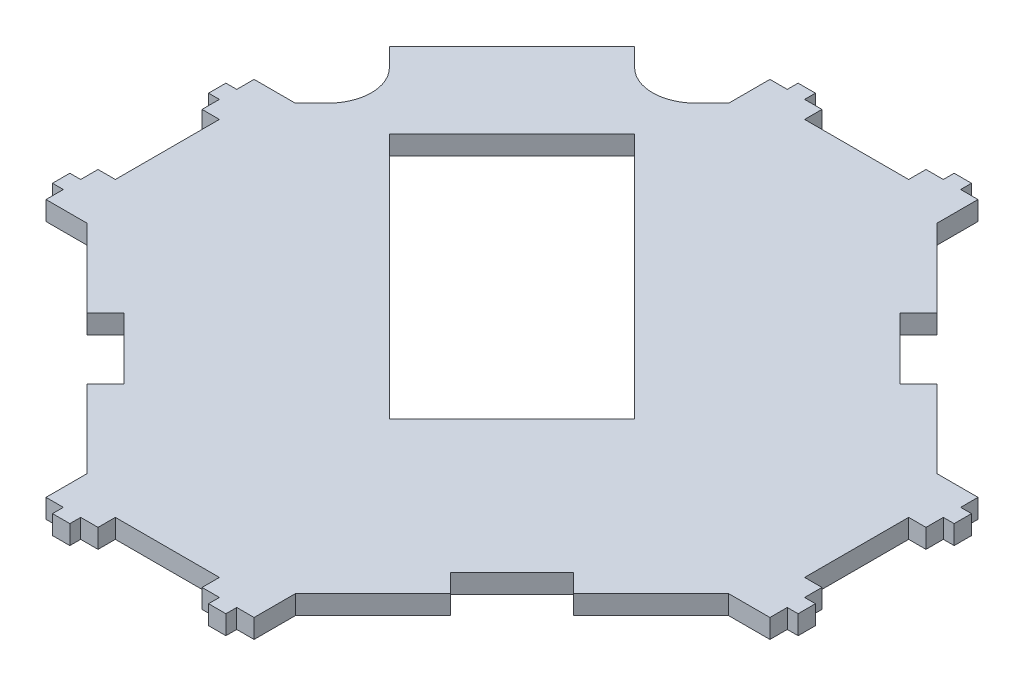
SolidWorks part; units mm, degrees
material "cardboard"
ref_plane "Front Plane" through (0, 0, 0) normal (0, 0, 1) x (1, 0, 0)
ref_plane "Top Plane" through (0, 0, 0) normal (0, 1, 0) x (1, 0, 0)
ref_plane "Right Plane" through (0, 0, 0) normal (1, 0, 0) x (0, 0, -1)
sketch "Sketch1" plane through (0, 0, 0) normal (0, 1, 0) x (1, 0, 0)
  line L0 (73.5822, 10.383) -> (66.732, 6.4281)
  line L1 (99.0822, -13.617) -> (105.9323, -9.662)
  line L2 (114.232, 6.4281) -> (105.9323, 6.4281)
  line L3 (114.232, -9.662) -> (105.9323, -9.662)
  line L4 (66.732, 6.4281) -> (58.4323, 6.4281)
  line L5 (121.0822, 10.383) -> (114.232, 6.4281)
  line L6 (121.0822, -13.617) -> (114.232, -9.662)
  line L7 (99.0822, 10.383) -> (105.9323, 6.4281)
  line L8 (121.0822, 10.383) -> (133.8322, 10.383)
  line L9 (121.0822, -13.617) -> (157.8322, -13.617)
  line L10 (51.5822, 10.383) -> (58.4323, 6.4281)
  line L11 (51.5822, -13.617) -> (58.4323, -9.662)
  line L12 (73.5822, -13.617) -> (66.732, -9.662)
  line L13 (66.732, -9.662) -> (58.4323, -9.662)
  line L14 (73.5822, 10.383) -> (99.0822, 10.383)
  line L15 (73.5822, -13.617) -> (99.0822, -13.617)
  line L16 (-16.1678, 76.133) -> (-12.2129, 69.2829)
  line L17 (7.8322, 101.633) -> (3.8772, 108.4832)
  line L18 (-12.2129, 116.7829) -> (-12.2129, 108.4832)
  line L19 (3.8772, 116.7829) -> (3.8772, 108.4832)
  line L20 (-12.2129, 69.2829) -> (-12.2129, 60.9832)
  line L21 (-16.1678, 123.633) -> (-12.2129, 116.7829)
  line L22 (7.8322, 123.633) -> (3.8772, 116.7829)
  line L23 (-16.1678, 101.633) -> (-12.2129, 108.4832)
  line L24 (-16.1678, 123.633) -> (-16.1678, 136.383)
  line L25 (7.8322, 123.633) -> (7.8322, 160.383)
  line L26 (-16.1678, 54.133) -> (-12.2129, 60.9832)
  line L27 (7.8322, 54.133) -> (3.8772, 60.9832)
  line L28 (7.8322, 76.133) -> (3.8772, 69.2829)
  line L29 (3.8772, 69.2829) -> (3.8772, 60.9832)
  line L30 (-16.1678, 76.133) -> (-16.1678, 101.633)
  line L31 (7.8322, 76.133) -> (7.8322, 101.633)
  line L32 (86.3322, 35.383) -> (86.3322, 15.383)
  line L33 (85.3322, 35.383) -> (85.3322, 29.383)
  line L34 (32.8322, 10.383) -> (38.8322, 10.383)
  line L35 (85.3322, 29.383) -> (87.3322, 29.383)
  line L36 (37.5822, 10.383) -> (37.5822, 8.383)
  line L37 (38.8322, 10.383) -> (51.5822, 10.383)
  line L38 (133.8322, 10.383) -> (133.8322, -13.617)
  line L39 (133.8322, 10.383) -> (157.8322, 10.383)
  line L40 (157.8322, 10.383) -> (157.8322, 8.383)
  line L41 (-32.6642, 12.7373) -> (-4.1678, -15.7591)
  line L42 (-32.6642, 12.7373) -> (-18.5221, 26.8794)
  line L43 (-4.1678, -15.7591) -> (9.9743, -1.617)
  line L44 (-18.5221, 26.8794) -> (9.9743, -1.617)
  line L45 (133.8322, 10.383) -> (133.8322, 35.383)
  line L46 (35.8322, 35.383) -> (157.8322, 35.383)
  line L47 (157.8322, 35.383) -> (157.8322, 10.383)
  line L48 (87.3322, 29.383) -> (87.3322, 21.383)
  line L49 (133.8322, 35.383) -> (133.8322, 59.383)
  line L50 (133.8322, 59.383) -> (142.8322, 59.383)
  line L51 (38.8322, 35.383) -> (38.8322, 15.383)
  line L52 (157.8322, 59.383) -> (157.8322, 49.705)
  line L53 (142.8322, 59.383) -> (142.8322, 61.583)
  line L54 (148.8322, 61.583) -> (148.8322, 59.383)
  line L55 (148.8322, 59.383) -> (157.8322, 59.383)
  line L56 (-63.1678, 136.383) -> (-63.1678, 111.883)
  line L57 (-43.1678, 111.883) -> (-43.1678, 136.383)
  line L58 (87.3322, 21.383) -> (85.3322, 21.383)
  line L59 (133.8322, -13.617) -> (133.8322, -38.617)
  line L60 (142.8322, -38.617) -> (148.8322, -38.617)
  line L61 (157.8322, -38.617) -> (157.8322, -13.617)
  line L62 (38.8322, -38.617) -> (38.8322, -18.617)
  line L63 (133.8322, -38.617) -> (133.8322, -39.797)
  line L64 (148.8322, -39.797) -> (157.8322, -39.797)
  line L65 (157.8322, -39.797) -> (157.8322, -38.617)
  line L66 (142.8322, -39.797) -> (142.8322, -38.617)
  line L67 (148.8322, -39.797) -> (148.8322, -38.617)
  line L68 (-42.3478, -139.617) -> (-42.3478, -148.617)
  line L69 (85.3322, 21.383) -> (85.3322, 15.383)
  line L70 (85.3322, 10.383) -> (85.3322, 2.383)
  line L71 (38.8322, -13.617) -> (51.5822, -13.617)
  line L72 (32.8322, -13.617) -> (38.8322, -13.617)
  line L73 (86.306, 10.383) -> (86.306, -13.617)
  line L74 (85.3322, 2.383) -> (87.3322, 2.383)
  line L75 (87.3322, 2.383) -> (87.3322, -5.617)
  line L76 (87.3322, -5.617) -> (85.3322, -5.617)
  line L77 (131.8322, 10.383) -> (131.8322, 2.383)
  line L78 (131.8322, 2.383) -> (135.8322, 2.383)
  line L79 (34.0122, 160.383) -> (34.0122, 151.383)
  line L80 (33.8322, 33.383) -> (33.8322, 17.383)
  line L81 (35.8322, 15.383) -> (133.8322, 15.383)
  line L82 (37.5822, 22.383) -> (37.5822, 15.383)
  line L83 (38.8322, 28.383) -> (35.8322, 28.383)
  line L84 (35.8322, 28.383) -> (35.8322, 22.383)
  line L85 (40.0822, 4.383) -> (37.5822, 4.383)
  line L86 (1.8322, -43.367) -> (1.8322, -41.367)
  line L87 (37.5822, -7.617) -> (40.0822, -7.617)
  line L88 (40.0822, 4.383) -> (40.0822, -7.617)
  line L89 (38.8322, 10.383) -> (38.8322, 4.383)
  line L90 (37.5822, 8.383) -> (40.0822, 8.383)
  line L91 (40.0822, 8.383) -> (40.0822, 6.383)
  line L92 (40.0822, 6.383) -> (37.5822, 6.383)
  line L93 (37.5822, 6.383) -> (37.5822, 4.383)
  line L94 (37.5822, -9.617) -> (37.5822, -7.617)
  line L95 (40.0822, -9.617) -> (37.5822, -9.617)
  line L96 (40.0822, -11.617) -> (40.0822, -9.617)
  line L97 (37.5822, -11.617) -> (40.0822, -11.617)
  line L98 (37.5822, -13.617) -> (37.5822, -11.617)
  line L99 (135.8322, 2.383) -> (135.8322, -5.617)
  line L100 (135.8322, -5.617) -> (131.8322, -5.617)
  line L101 (131.8322, -5.617) -> (131.8322, -13.617)
  line L102 (133.8322, 12.383) -> (141.8322, 12.383)
  line L103 (141.8322, 12.383) -> (141.8322, 8.383)
  line L104 (141.8322, 8.383) -> (149.8322, 8.383)
  line L105 (149.8322, 8.383) -> (149.8322, 12.383)
  line L106 (149.8322, 12.383) -> (157.8322, 12.383)
  line L107 (132.3322, 35.383) -> (132.3322, 29.383)
  line L108 (132.3322, 29.383) -> (135.3322, 29.383)
  line L109 (135.3322, 29.383) -> (135.3322, 21.383)
  line L110 (135.3322, 21.383) -> (132.3322, 21.383)
  line L111 (132.3322, 21.383) -> (132.3322, 15.383)
  line L112 (85.3322, -5.617) -> (85.3322, -13.617)
  line L113 (85.3322, -24.617) -> (85.3322, -18.617)
  line L114 (86.3322, -38.617) -> (86.3322, -18.617)
  line L115 (87.3322, -24.617) -> (85.3322, -24.617)
  line L116 (87.3322, -32.617) -> (87.3322, -24.617)
  line L117 (149.8322, -15.617) -> (157.8322, -15.617)
  line L118 (149.8322, -11.617) -> (149.8322, -15.617)
  line L119 (141.8322, -11.617) -> (149.8322, -11.617)
  line L120 (141.8322, -15.617) -> (141.8322, -11.617)
  line L121 (133.8322, -15.617) -> (141.8322, -15.617)
  line L122 (132.3322, -24.617) -> (132.3322, -18.617)
  line L123 (135.3322, -24.617) -> (132.3322, -24.617)
  line L124 (37.5822, 35.383) -> (37.5822, 28.383)
  line L125 (38.8322, 22.383) -> (35.8322, 22.383)
  line L126 (133.8322, -38.617) -> (35.8322, -38.617)
  line L127 (33.8322, -36.617) -> (33.8322, -20.617)
  line L128 (35.8322, -18.617) -> (133.8322, -18.617)
  line L129 (135.3322, -32.617) -> (135.3322, -24.617)
  line L130 (132.3322, -32.617) -> (135.3322, -32.617)
  line L131 (132.3322, -38.617) -> (132.3322, -32.617)
  line L132 (85.3322, -32.617) -> (87.3322, -32.617)
  line L133 (85.3322, -38.617) -> (85.3322, -32.617)
  line L134 (133.8322, 37.383) -> (141.8322, 37.383)
  line L135 (141.8322, 37.383) -> (141.8322, 33.383)
  line L136 (141.8322, 33.383) -> (149.8322, 33.383)
  line L137 (149.8322, 33.383) -> (149.8322, 37.383)
  line L138 (149.8322, 37.383) -> (157.8322, 37.383)
  line L139 (-48.6678, 132.133) -> (-48.6678, 116.133)
  line L140 (-60.1678, 132.133) -> (-57.6678, 132.133)
  line L141 (-60.1678, 132.133) -> (-60.1678, 116.133)
  line L142 (-60.1678, 116.133) -> (-57.6678, 116.133)
  line L143 (-57.6678, 132.133) -> (-57.6678, 116.133)
  line L144 (37.5822, -25.617) -> (37.5822, -18.617)
  line L145 (38.8322, -25.617) -> (35.8322, -25.617)
  line L146 (35.8322, -31.617) -> (35.8322, -25.617)
  line L147 (38.8322, -31.617) -> (35.8322, -31.617)
  line L148 (37.5822, -38.617) -> (37.5822, -31.617)
  line L149 (192.8322, 3.383) -> (192.8322, -6.617)
  line L150 (187.8322, 8.383) -> (157.8322, 8.383)
  line L151 (187.8322, -11.617) -> (157.8322, -11.617)
  line L152 (187.8322, 8.383) -> (192.8322, 3.383)
  line L153 (192.8322, -6.617) -> (187.8322, -11.617)
  line L154 (157.8322, -11.617) -> (157.8322, -13.617)
  line L155 (133.8322, 61.583) -> (142.8322, 61.583)
  line L156 (133.8322, 61.583) -> (133.8322, 63.583)
  line L157 (133.8322, 63.583) -> (157.8322, 63.583)
  line L158 (157.8322, 63.583) -> (157.8322, 61.583)
  line L159 (148.8322, 61.583) -> (157.8322, 61.583)
  line L160 (-46.1678, 116.133) -> (-48.6678, 116.133)
  line L161 (-46.1678, 132.133) -> (-46.1678, 116.133)
  line L162 (-46.1678, 132.133) -> (-48.6678, 132.133)
  line L163 (151.2322, 49.705) -> (157.8322, 49.705)
  line L164 (151.2322, 49.705) -> (151.2322, 45.205)
  line L165 (151.2322, 45.205) -> (157.8322, 45.205)
  line L166 (157.8322, 45.205) -> (157.8322, 35.383)
  line L167 (7.8322, -79.367) -> (3.8772, -72.5168)
  line L168 (-16.1678, -104.867) -> (-12.2129, -111.7171)
  line L169 (3.8772, -120.0168) -> (3.8772, -111.7171)
  line L170 (7.8322, -38.617) -> (7.8322, -44.617)
  line L171 (7.8322, -43.367) -> (5.8322, -43.367)
  line L172 (7.8322, -44.617) -> (7.8322, -57.367)
  line L173 (-12.2129, -120.0168) -> (-12.2129, -111.7171)
  line L174 (3.8772, -72.5168) -> (3.8772, -64.2171)
  line L175 (7.8322, -126.867) -> (3.8772, -120.0168)
  line L176 (-16.1678, -126.867) -> (-12.2129, -120.0168)
  line L177 (7.8322, -104.867) -> (3.8772, -111.7171)
  line L178 (7.8322, -126.867) -> (7.8322, -139.617)
  line L179 (-16.1678, -126.867) -> (-16.1678, -163.617)
  line L180 (7.8322, -57.367) -> (3.8772, -64.2171)
  line L181 (-16.1678, -57.367) -> (-12.2129, -64.2171)
  line L182 (32.8322, -44.617) -> (12.8322, -44.617)
  line L183 (-16.1678, -79.367) -> (-12.2129, -72.5168)
  line L184 (-12.2129, -72.5168) -> (-12.2129, -64.2171)
  line L185 (7.8322, -79.367) -> (7.8322, -104.867)
  line L186 (-16.1678, -79.367) -> (-16.1678, -104.867)
  line L187 (32.8322, -92.117) -> (12.8322, -92.117)
  line L188 (32.8322, -91.117) -> (26.8322, -91.117)
  line L189 (26.8322, -91.117) -> (26.8322, -93.117)
  line L190 (7.8322, -139.617) -> (-16.1678, -139.617)
  line L191 (7.8322, -139.617) -> (7.8322, -163.617)
  line L192 (7.8322, -163.617) -> (5.8322, -163.617)
  line L193 (7.8322, -139.617) -> (32.8322, -139.617)
  line L194 (32.8322, -41.617) -> (32.8322, -163.617)
  line L195 (-41.1678, -44.617) -> (-21.1678, -44.617)
  line L196 (32.8322, -163.617) -> (7.8322, -163.617)
  line L197 (26.8322, -93.117) -> (18.8322, -93.117)
  line L198 (32.8322, -139.617) -> (56.8322, -139.617)
  line L199 (56.8322, -139.617) -> (56.8322, -148.617)
  line L200 (56.8322, -163.617) -> (47.1541, -163.617)
  line L201 (56.8322, -148.617) -> (59.0322, -148.617)
  line L202 (59.0322, -154.617) -> (56.8322, -154.617)
  line L203 (56.8322, -154.617) -> (56.8322, -163.617)
  line L204 (-16.1678, -44.617) -> (-16.1678, -57.367)
  line L205 (-16.1678, -38.617) -> (-16.1678, -44.617)
  line L206 (18.8322, -93.117) -> (18.8322, -91.117)
  line L207 (-16.1678, -139.617) -> (-41.1678, -139.617)
  line L208 (-41.1678, -148.617) -> (-41.1678, -154.617)
  line L209 (34.0122, 145.383) -> (34.0122, 136.383)
  line L210 (30.8322, -39.617) -> (14.8322, -39.617)
  line L211 (12.8322, -41.617) -> (12.8322, -139.617)
  line L212 (19.8322, -43.367) -> (12.8322, -43.367)
  line L213 (25.8322, -44.617) -> (25.8322, -41.617)
  line L214 (25.8322, -41.617) -> (19.8322, -41.617)
  line L215 (1.8322, -45.867) -> (1.8322, -43.367)
  line L216 (-41.1678, -163.617) -> (-16.1678, -163.617)
  line L217 (-10.1678, -43.367) -> (-10.1678, -45.867)
  line L218 (1.8322, -45.867) -> (-10.1678, -45.867)
  line L219 (7.8322, -44.617) -> (1.8322, -44.617)
  line L220 (5.8322, -43.367) -> (5.8322, -45.867)
  line L221 (5.8322, -45.867) -> (3.8322, -45.867)
  line L222 (3.8322, -45.867) -> (3.8322, -43.367)
  line L223 (3.8322, -43.367) -> (1.8322, -43.367)
  line L224 (-12.1678, -43.367) -> (-10.1678, -43.367)
  line L225 (-12.1678, -45.867) -> (-12.1678, -43.367)
  line L226 (-14.1678, -45.867) -> (-12.1678, -45.867)
  line L227 (-14.1678, -43.367) -> (-14.1678, -45.867)
  line L228 (-16.1678, -43.367) -> (-14.1678, -43.367)
  line L229 (-41.1678, -139.617) -> (-42.3478, -139.617)
  line L230 (-42.3478, -154.617) -> (-42.3478, -163.617)
  line L231 (-42.3478, -163.617) -> (-41.1678, -163.617)
  line L232 (-42.3478, -148.617) -> (-41.1678, -148.617)
  line L233 (-42.3478, -154.617) -> (-41.1678, -154.617)
  line L234 (-166.1678, 36.563) -> (-157.1678, 36.563)
  line L235 (18.8322, -91.117) -> (12.8322, -91.117)
  line L236 (7.8322, -91.117) -> (-0.1678, -91.117)
  line L237 (7.8322, -92.0907) -> (-16.1678, -92.0907)
  line L238 (-0.1678, -91.117) -> (-0.1678, -93.117)
  line L239 (-0.1678, -93.117) -> (-8.1678, -93.117)
  line L240 (-8.1678, -93.117) -> (-8.1678, -91.117)
  line L241 (7.8322, -137.617) -> (-0.1678, -137.617)
  line L242 (-0.1678, -137.617) -> (-0.1678, -141.617)
  line L243 (-0.1678, -141.617) -> (-8.1678, -141.617)
  line L244 (-8.1678, -141.617) -> (-8.1678, -137.617)
  line L245 (-8.1678, -137.617) -> (-16.1678, -137.617)
  line L246 (9.8322, -139.617) -> (9.8322, -147.617)
  line L247 (9.8322, -147.617) -> (5.8322, -147.617)
  line L248 (5.8322, -147.617) -> (5.8322, -155.617)
  line L249 (5.8322, -155.617) -> (9.8322, -155.617)
  line L250 (9.8322, -155.617) -> (9.8322, -163.617)
  line L251 (32.8322, -138.117) -> (26.8322, -138.117)
  line L252 (26.8322, -138.117) -> (26.8322, -141.117)
  line L253 (26.8322, -141.117) -> (18.8322, -141.117)
  line L254 (32.8322, -43.367) -> (25.8322, -43.367)
  line L255 (19.8322, -44.617) -> (19.8322, -41.617)
  line L256 (-41.1678, -139.617) -> (-41.1678, -41.617)
  line L257 (-39.1678, -39.617) -> (-23.1678, -39.617)
  line L258 (-21.1678, -41.617) -> (-21.1678, -139.617)
  line L259 (18.8322, -141.117) -> (18.8322, -138.117)
  line L260 (18.8322, -138.117) -> (12.8322, -138.117)
  line L261 (-8.1678, -91.117) -> (-16.1678, -91.117)
  line L262 (-27.1678, -91.117) -> (-21.1678, -91.117)
  line L263 (-41.1678, -92.117) -> (-21.1678, -92.117)
  line L264 (-27.1678, -93.117) -> (-27.1678, -91.117)
  line L265 (-35.1678, -93.117) -> (-27.1678, -93.117)
  line L266 (-18.1678, -155.617) -> (-18.1678, -163.617)
  line L267 (-14.1678, -155.617) -> (-18.1678, -155.617)
  line L268 (-14.1678, -147.617) -> (-14.1678, -155.617)
  line L269 (-18.1678, -147.617) -> (-14.1678, -147.617)
  line L270 (-18.1678, -139.617) -> (-18.1678, -147.617)
  line L271 (-27.1678, -138.117) -> (-21.1678, -138.117)
  line L272 (-27.1678, -141.117) -> (-27.1678, -138.117)
  line L273 (-35.1678, -141.117) -> (-27.1678, -141.117)
  line L274 (-28.1678, -43.367) -> (-21.1678, -43.367)
  line L275 (-28.1678, -44.617) -> (-28.1678, -41.617)
  line L276 (-34.1678, -41.617) -> (-28.1678, -41.617)
  line L277 (-34.1678, -44.617) -> (-34.1678, -41.617)
  line L278 (-41.1678, -43.367) -> (-34.1678, -43.367)
  line L279 (-35.1678, -138.117) -> (-35.1678, -141.117)
  line L280 (-41.1678, -138.117) -> (-35.1678, -138.117)
  line L281 (-35.1678, -91.117) -> (-35.1678, -93.117)
  line L282 (-41.1678, -91.117) -> (-35.1678, -91.117)
  line L283 (34.8322, -139.617) -> (34.8322, -147.617)
  line L284 (34.8322, -147.617) -> (30.8322, -147.617)
  line L285 (30.8322, -147.617) -> (30.8322, -155.617)
  line L286 (30.8322, -155.617) -> (34.8322, -155.617)
  line L287 (34.8322, -155.617) -> (34.8322, -163.617)
  line L288 (0.8322, -198.617) -> (-9.1678, -198.617)
  line L289 (5.8322, -193.617) -> (5.8322, -163.617)
  line L290 (-14.1678, -193.617) -> (-14.1678, -163.617)
  line L291 (5.8322, -193.617) -> (0.8322, -198.617)
  line L292 (-9.1678, -198.617) -> (-14.1678, -193.617)
  line L293 (-14.1678, -163.617) -> (-16.1678, -163.617)
  line L294 (59.0322, -139.617) -> (59.0322, -148.617)
  line L295 (59.0322, -139.617) -> (61.0322, -139.617)
  line L296 (61.0322, -139.617) -> (61.0322, -163.617)
  line L297 (61.0322, -163.617) -> (59.0322, -163.617)
  line L298 (59.0322, -154.617) -> (59.0322, -163.617)
  line L299 (-41.1678, -13.617) -> (-47.1678, -13.617)
  line L300 (-45.9178, -13.617) -> (-45.9178, -11.617)
  line L301 (-47.1678, -13.617) -> (-59.9178, -13.617)
  line L302 (47.1541, -157.017) -> (47.1541, -163.617)
  line L303 (47.1541, -157.017) -> (42.6541, -157.017)
  line L304 (-47.1678, -38.617) -> (-47.1678, -18.617)
  line L305 (42.6541, -157.017) -> (42.6541, -163.617)
  line L306 (42.6541, -163.617) -> (32.8322, -163.617)
  line L307 (-81.9178, -13.617) -> (-75.0677, -9.662)
  line L308 (-107.4178, 10.383) -> (-114.268, 6.4281)
  line L309 (-122.5677, -9.662) -> (-114.268, -9.662)
  line L310 (-122.5677, 6.4281) -> (-114.268, 6.4281)
  line L311 (-75.0677, -9.662) -> (-66.768, -9.662)
  line L312 (-129.4178, -13.617) -> (-122.5677, -9.662)
  line L313 (-129.4178, 10.383) -> (-122.5677, 6.4281)
  line L314 (-107.4178, -13.617) -> (-114.268, -9.662)
  line L315 (-129.4178, -13.617) -> (-142.1678, -13.617)
  line L316 (-47.1678, 35.383) -> (-47.1678, 15.383)
  line L317 (-129.4178, 10.383) -> (-166.1678, 10.383)
  line L318 (-59.9178, -13.617) -> (-66.768, -9.662)
  line L319 (-59.9178, 10.383) -> (-66.768, 6.4281)
  line L320 (-81.9178, 10.383) -> (-75.0677, 6.4281)
  line L321 (-75.0677, 6.4281) -> (-66.768, 6.4281)
  line L322 (-81.9178, -13.617) -> (-107.4178, -13.617)
  line L323 (-81.9178, 10.383) -> (-107.4178, 10.383)
  line L324 (-94.6678, -38.617) -> (-94.6678, -18.617)
  line L325 (-47.1678, 10.383) -> (-59.9178, 10.383)
  line L326 (-41.1678, 10.383) -> (-47.1678, 10.383)
  line L327 (-93.6678, -38.617) -> (-93.6678, -32.617)
  line L328 (-93.6678, -32.617) -> (-95.6678, -32.617)
  line L329 (-142.1678, -13.617) -> (-142.1678, 10.383)
  line L330 (-142.1678, -13.617) -> (-166.1678, -13.617)
  line L331 (-166.1678, -13.617) -> (-166.1678, -11.617)
  line L332 (-142.1678, -13.617) -> (-142.1678, -38.617)
  line L333 (133.8322, -39.797) -> (142.8322, -39.797)
  line L334 (-42.1678, -36.617) -> (-42.1678, -20.617)
  line L335 (-44.1678, -18.617) -> (-142.1678, -18.617)
  line L336 (-45.9178, -25.617) -> (-45.9178, -18.617)
  line L337 (-47.1678, -31.617) -> (-44.1678, -31.617)
  line L338 (-44.1678, -31.617) -> (-44.1678, -25.617)
  line L339 (-48.4178, -7.617) -> (-45.9178, -7.617)
  line L340 (-44.1678, -38.617) -> (-166.1678, -38.617)
  line L341 (-45.9178, 4.383) -> (-48.4178, 4.383)
  line L342 (-48.4178, -7.617) -> (-48.4178, 4.383)
  line L343 (-47.1678, -13.617) -> (-47.1678, -7.617)
  line L344 (-45.9178, -11.617) -> (-48.4178, -11.617)
  line L345 (-48.4178, -11.617) -> (-48.4178, -9.617)
  line L346 (-48.4178, -9.617) -> (-45.9178, -9.617)
  line L347 (-45.9178, -9.617) -> (-45.9178, -7.617)
  line L348 (-45.9178, 6.383) -> (-45.9178, 4.383)
  line L349 (-48.4178, 6.383) -> (-45.9178, 6.383)
  line L350 (-48.4178, 8.383) -> (-48.4178, 6.383)
  line L351 (-45.9178, 8.383) -> (-48.4178, 8.383)
  line L352 (-45.9178, 10.383) -> (-45.9178, 8.383)
  line L353 (-166.1678, -38.617) -> (-166.1678, -13.617)
  line L354 (-95.6678, -32.617) -> (-95.6678, -24.617)
  line L355 (-142.1678, -38.617) -> (-142.1678, -62.617)
  line L356 (-142.1678, -62.617) -> (-151.1678, -62.617)
  line L357 (-166.1678, -62.617) -> (-166.1678, -52.9389)
  line L358 (-151.1678, -62.617) -> (-151.1678, -64.817)
  line L359 (-157.1678, -64.817) -> (-157.1678, -62.617)
  line L360 (-157.1678, -62.617) -> (-166.1678, -62.617)
  line L361 (-95.6678, -24.617) -> (-93.6678, -24.617)
  line L362 (-142.1678, 10.383) -> (-142.1678, 35.383)
  line L363 (-151.1678, 35.383) -> (-157.1678, 35.383)
  line L364 (-166.1678, 35.383) -> (-166.1678, 10.383)
  line L365 (-142.1678, 35.383) -> (-142.1678, 36.563)
  line L366 (-166.1678, 36.563) -> (-166.1678, 35.383)
  line L367 (-151.1678, 36.563) -> (-151.1678, 35.383)
  line L368 (-157.1678, 36.563) -> (-157.1678, 35.383)
  line L369 (-151.1678, 36.563) -> (-142.1678, 36.563)
  line L370 (-93.6678, -24.617) -> (-93.6678, -18.617)
  line L371 (-93.6678, -13.617) -> (-93.6678, -5.617)
  line L372 (-94.6416, -13.617) -> (-94.6416, 10.383)
  line L373 (-93.6678, -5.617) -> (-95.6678, -5.617)
  line L374 (-45.9178, -38.617) -> (-45.9178, -31.617)
  line L375 (-47.1678, -25.617) -> (-44.1678, -25.617)
  line L376 (-142.1678, 35.383) -> (-44.1678, 35.383)
  line L377 (-42.1678, 33.383) -> (-42.1678, 17.383)
  line L378 (-44.1678, 15.383) -> (-142.1678, 15.383)
  line L379 (-95.6678, -5.617) -> (-95.6678, 2.383)
  line L380 (-95.6678, 2.383) -> (-93.6678, 2.383)
  line L381 (-140.1678, -13.617) -> (-140.1678, -5.617)
  line L382 (-140.1678, -5.617) -> (-144.1678, -5.617)
  line L383 (-144.1678, -5.617) -> (-144.1678, 2.383)
  line L384 (-144.1678, 2.383) -> (-140.1678, 2.383)
  line L385 (-140.1678, 2.383) -> (-140.1678, 10.383)
  line L386 (-142.1678, -15.617) -> (-150.1678, -15.617)
  line L387 (-150.1678, -15.617) -> (-150.1678, -11.617)
  line L388 (-150.1678, -11.617) -> (-158.1678, -11.617)
  line L389 (-158.1678, -11.617) -> (-158.1678, -15.617)
  line L390 (-158.1678, -15.617) -> (-166.1678, -15.617)
  line L391 (-140.6678, -38.617) -> (-140.6678, -32.617)
  line L392 (-41.1678, 88.883) -> (-21.1678, 88.883)
  line L393 (-41.1678, 87.883) -> (-35.1678, 87.883)
  line L394 (-45.9178, 22.383) -> (-45.9178, 15.383)
  line L395 (-47.1678, 22.383) -> (-44.1678, 22.383)
  line L396 (-44.1678, 28.383) -> (-44.1678, 22.383)
  line L397 (-47.1678, 28.383) -> (-44.1678, 28.383)
  line L398 (-45.9178, 35.383) -> (-45.9178, 28.383)
  line L399 (-140.6678, -32.617) -> (-143.6678, -32.617)
  line L400 (-143.6678, -32.617) -> (-143.6678, -24.617)
  line L401 (-143.6678, -24.617) -> (-140.6678, -24.617)
  line L402 (-140.6678, -24.617) -> (-140.6678, -18.617)
  line L403 (-93.6678, 2.383) -> (-93.6678, 10.383)
  line L404 (-93.6678, 21.383) -> (-93.6678, 15.383)
  line L405 (-94.6678, 35.383) -> (-94.6678, 15.383)
  line L406 (-95.6678, 21.383) -> (-93.6678, 21.383)
  line L407 (-95.6678, 29.383) -> (-95.6678, 21.383)
  line L408 (-158.1678, 12.383) -> (-166.1678, 12.383)
  line L409 (-158.1678, 8.383) -> (-158.1678, 12.383)
  line L410 (-150.1678, 8.383) -> (-158.1678, 8.383)
  line L411 (-150.1678, 12.383) -> (-150.1678, 8.383)
  line L412 (-142.1678, 12.383) -> (-150.1678, 12.383)
  line L413 (-140.6678, 21.383) -> (-140.6678, 15.383)
  line L414 (-143.6678, 21.383) -> (-140.6678, 21.383)
  line L415 (-143.6678, 29.383) -> (-143.6678, 21.383)
  line L416 (-140.6678, 29.383) -> (-143.6678, 29.383)
  line L417 (-140.6678, 35.383) -> (-140.6678, 29.383)
  line L418 (-93.6678, 29.383) -> (-95.6678, 29.383)
  line L419 (-93.6678, 35.383) -> (-93.6678, 29.383)
  line L420 (-142.1678, -40.617) -> (-150.1678, -40.617)
  line L421 (-150.1678, -40.617) -> (-150.1678, -36.617)
  line L422 (-150.1678, -36.617) -> (-158.1678, -36.617)
  line L423 (-158.1678, -36.617) -> (-158.1678, -40.617)
  line L424 (-158.1678, -40.617) -> (-166.1678, -40.617)
  line L425 (-16.1678, 40.133) -> (-14.1678, 40.133)
  line L426 (-35.1678, 87.883) -> (-35.1678, 89.883)
  line L427 (-16.1678, 136.383) -> (7.8322, 136.383)
  line L428 (-16.1678, 136.383) -> (-16.1678, 160.383)
  line L429 (-16.1678, 160.383) -> (-14.1678, 160.383)
  line L430 (-16.1678, 136.383) -> (-41.1678, 136.383)
  line L431 (-41.1678, 136.383) -> (-41.1678, 160.383)
  line L432 (-41.1678, 160.383) -> (-16.1678, 160.383)
  line L433 (-41.1678, 136.383) -> (-41.1678, 41.383)
  line L434 (-41.1678, 41.383) -> (-21.1678, 41.383)
  line L435 (-21.1678, 41.383) -> (-21.1678, 136.383)
  line L436 (-35.1678, 89.883) -> (-27.1678, 89.883)
  line L437 (-41.1678, 136.383) -> (-65.1678, 136.383)
  line L438 (-65.1678, 136.383) -> (-65.1678, 145.383)
  line L439 (-65.1678, 160.383) -> (-55.4898, 160.383)
  line L440 (-65.1678, 145.383) -> (-67.3678, 145.383)
  line L441 (-67.3678, 151.383) -> (-65.1678, 151.383)
  line L442 (-65.1678, 151.383) -> (-65.1678, 160.383)
  line L443 (-63.1678, 111.883) -> (-43.1678, 111.883)
  line L444 (32.8322, 41.383) -> (12.8322, 41.383)
  line L445 (-27.1678, 89.883) -> (-27.1678, 87.883)
  line L446 (32.8322, 136.383) -> (32.8322, 41.383)
  line L447 (12.8322, 41.383) -> (12.8322, 136.383)
  line L448 (7.8322, 136.383) -> (32.8322, 136.383)
  line L449 (32.8322, 145.383) -> (32.8322, 151.383)
  line L450 (32.8322, 160.383) -> (7.8322, 160.383)
  line L451 (7.8322, 35.383) -> (7.8322, 54.133)
  line L452 (32.8322, 136.383) -> (34.0122, 136.383)
  line L453 (34.0122, 160.383) -> (32.8322, 160.383)
  line L454 (34.0122, 145.383) -> (32.8322, 145.383)
  line L455 (34.0122, 151.383) -> (32.8322, 151.383)
  line L456 (-41.1678, 41.383) -> (-41.1678, 38.383)
  line L457 (-39.1678, 36.383) -> (-23.1678, 36.383)
  line L458 (-21.1678, 38.383) -> (-21.1678, 41.383)
  line L459 (30.8322, 36.383) -> (14.8322, 36.383)
  line L460 (12.8322, 38.383) -> (12.8322, 41.383)
  line L461 (-10.1678, 42.633) -> (-10.1678, 40.133)
  line L462 (-27.1678, 87.883) -> (-21.1678, 87.883)
  line L463 (1.8322, 40.133) -> (1.8322, 42.633)
  line L464 (-10.1678, 42.633) -> (1.8322, 42.633)
  line L465 (-16.1678, 41.383) -> (-10.1678, 41.383)
  line L466 (-14.1678, 40.133) -> (-14.1678, 42.633)
  line L467 (-14.1678, 42.633) -> (-12.1678, 42.633)
  line L468 (-12.1678, 42.633) -> (-12.1678, 40.133)
  line L469 (-12.1678, 40.133) -> (-10.1678, 40.133)
  line L470 (3.8322, 40.133) -> (1.8322, 40.133)
  line L471 (3.8322, 42.633) -> (3.8322, 40.133)
  line L472 (5.8322, 42.633) -> (3.8322, 42.633)
  line L473 (5.8322, 40.133) -> (5.8322, 42.633)
  line L474 (7.8322, 40.133) -> (5.8322, 40.133)
  line L475 (-16.1678, 87.883) -> (-8.1678, 87.883)
  line L476 (-16.1678, 88.8568) -> (7.8322, 88.8568)
  line L477 (-8.1678, 87.883) -> (-8.1678, 89.883)
  line L478 (-8.1678, 89.883) -> (-0.1678, 89.883)
  line L479 (-0.1678, 89.883) -> (-0.1678, 87.883)
  line L480 (-16.1678, 134.383) -> (-8.1678, 134.383)
  line L481 (-8.1678, 134.383) -> (-8.1678, 138.383)
  line L482 (-8.1678, 138.383) -> (-0.1678, 138.383)
  line L483 (-0.1678, 138.383) -> (-0.1678, 134.383)
  line L484 (-0.1678, 134.383) -> (7.8322, 134.383)
  line L485 (-18.1678, 136.383) -> (-18.1678, 144.383)
  line L486 (-18.1678, 144.383) -> (-14.1678, 144.383)
  line L487 (-14.1678, 144.383) -> (-14.1678, 152.383)
  line L488 (-14.1678, 152.383) -> (-18.1678, 152.383)
  line L489 (-18.1678, 152.383) -> (-18.1678, 160.383)
  line L490 (-41.1678, 134.883) -> (-35.1678, 134.883)
  line L491 (-35.1678, 134.883) -> (-35.1678, 137.883)
  line L492 (-35.1678, 137.883) -> (-27.1678, 137.883)
  line L493 (-27.1678, 137.883) -> (-27.1678, 134.883)
  line L494 (-27.1678, 134.883) -> (-21.1678, 134.883)
  line L495 (-0.1678, 87.883) -> (7.8322, 87.883)
  line L496 (18.8322, 87.883) -> (12.8322, 87.883)
  line L497 (32.8322, 88.883) -> (12.8322, 88.883)
  line L498 (18.8322, 89.883) -> (18.8322, 87.883)
  line L499 (26.8322, 89.883) -> (18.8322, 89.883)
  line L500 (-41.1678, 40.133) -> (-34.1678, 40.133)
  line L501 (25.8322, 38.383) -> (19.8322, 38.383)
  line L502 (19.8322, 40.133) -> (12.8322, 40.133)
  line L503 (-34.1678, 41.383) -> (-34.1678, 38.383)
  line L504 (-28.1678, 40.133) -> (-21.1678, 40.133)
  line L505 (9.8322, 152.383) -> (9.8322, 160.383)
  line L506 (5.8322, 152.383) -> (9.8322, 152.383)
  line L507 (5.8322, 144.383) -> (5.8322, 152.383)
  line L508 (9.8322, 144.383) -> (5.8322, 144.383)
  line L509 (9.8322, 136.383) -> (9.8322, 144.383)
  line L510 (18.8322, 134.883) -> (12.8322, 134.883)
  line L511 (18.8322, 137.883) -> (18.8322, 134.883)
  line L512 (26.8322, 137.883) -> (18.8322, 137.883)
  line L513 (26.8322, 134.883) -> (26.8322, 137.883)
  line L514 (32.8322, 134.883) -> (26.8322, 134.883)
  line L515 (26.8322, 87.883) -> (26.8322, 89.883)
  line L516 (32.8322, 87.883) -> (26.8322, 87.883)
  line L517 (7.8322, 35.383) -> (16.7966, 26.4186)
  line L518 (32.8322, -13.617) -> (23.8677, -22.5814)
  line L519 (-16.1678, -38.617) -> (-25.1323, -29.6525)
  line L520 (19.8322, 41.383) -> (19.8322, 38.383)
  line L521 (-28.1678, 41.383) -> (-28.1678, 38.383)
  line L522 (25.8322, 41.383) -> (25.8322, 38.383)
  line L523 (32.8322, 40.133) -> (25.8322, 40.133)
  line L524 (-43.1678, 136.383) -> (-43.1678, 144.383)
  line L525 (-43.1678, 144.383) -> (-39.1678, 144.383)
  line L526 (-39.1678, 144.383) -> (-39.1678, 152.383)
  line L527 (-39.1678, 152.383) -> (-43.1678, 152.383)
  line L528 (-43.1678, 152.383) -> (-43.1678, 160.383)
  line L529 (-63.1678, 134.883) -> (-56.1678, 134.883)
  line L530 (-56.1678, 134.883) -> (-56.1678, 137.883)
  line L531 (-56.1678, 137.883) -> (-50.1678, 137.883)
  line L532 (-50.1678, 137.883) -> (-50.1678, 134.883)
  line L533 (-50.1678, 134.883) -> (-43.1678, 134.883)
  line L534 (-16.1678, 35.383) -> (-16.1678, 54.133)
  line L535 (38.8322, -7.617) -> (38.8322, -13.617)
  line L536 (1.8322, 41.383) -> (7.8322, 41.383)
  line L537 (-47.1678, 4.383) -> (-47.1678, 10.383)
  line L538 (-10.1678, -44.617) -> (-16.1678, -44.617)
  line L539 (-9.1678, 195.383) -> (0.8322, 195.383)
  line L540 (-14.1678, 190.383) -> (-14.1678, 160.383)
  line L541 (5.8322, 190.383) -> (5.8322, 160.383)
  line L542 (-14.1678, 190.383) -> (-9.1678, 195.383)
  line L543 (0.8322, 195.383) -> (5.8322, 190.383)
  line L544 (129.5822, 54.383) -> (113.5822, 54.383)
  line L545 (129.5822, 54.383) -> (129.5822, 51.883)
  line L546 (-201.1678, -6.617) -> (-201.1678, 3.383)
  line L547 (-196.1678, -11.617) -> (-166.1678, -11.617)
  line L548 (-196.1678, 8.383) -> (-166.1678, 8.383)
  line L549 (-196.1678, -11.617) -> (-201.1678, -6.617)
  line L550 (-201.1678, 3.383) -> (-196.1678, 8.383)
  line L551 (-166.1678, 8.383) -> (-166.1678, 10.383)
  line L552 (-142.1678, -64.817) -> (-151.1678, -64.817)
  line L553 (-142.1678, -64.817) -> (-142.1678, -66.817)
  line L554 (-142.1678, -66.817) -> (-166.1678, -66.817)
  line L555 (-166.1678, -66.817) -> (-166.1678, -64.817)
  line L556 (5.8322, 160.383) -> (7.8322, 160.383)
  line L557 (-157.1678, -64.817) -> (-166.1678, -64.817)
  line L558 (129.5822, 51.883) -> (113.5822, 51.883)
  line L559 (113.5822, 54.383) -> (113.5822, 51.883)
  line L560 (129.5822, 42.883) -> (113.5822, 42.883)
  line L561 (129.5822, 40.383) -> (129.5822, 42.883)
  line L562 (129.5822, 40.383) -> (113.5822, 40.383)
  line L563 (113.5822, 40.383) -> (113.5822, 42.883)
  line L564 (132.3322, 57.383) -> (132.3322, 50.383)
  line L565 (132.3322, 50.383) -> (135.3322, 50.383)
  line L566 (-159.5678, -52.9389) -> (-166.1678, -52.9389)
  line L567 (-159.5678, -52.9389) -> (-159.5678, -48.4389)
  line L568 (-159.5678, -48.4389) -> (-166.1678, -48.4389)
  line L569 (-67.3678, 136.383) -> (-67.3678, 145.383)
  line L570 (-67.3678, 136.383) -> (-69.3678, 136.383)
  line L571 (-69.3678, 136.383) -> (-69.3678, 160.383)
  line L572 (-69.3678, 160.383) -> (-67.3678, 160.383)
  line L573 (-67.3678, 151.383) -> (-67.3678, 160.383)
  line L574 (-166.1678, -48.4389) -> (-166.1678, -38.617)
  line L575 (135.3322, 50.383) -> (135.3322, 44.383)
  line L576 (-50.5299, 122.2278) -> (-51.6678, 122.2278)
  line L577 (-55.8058, 126.2691) -> (-54.6678, 126.2691)
  line L578 (-55.8058, 126.2691) -> (-55.8058, 122.2278)
  line L579 (-55.8058, 122.2278) -> (-54.6678, 122.2278)
  line L580 (-54.6678, 126.2691) -> (-54.6678, 122.2278)
  line L581 (-51.6678, 126.2691) -> (-51.6678, 122.2278)
  line L582 (-50.5299, 126.2691) -> (-51.6678, 126.2691)
  line L583 (-50.5299, 126.2691) -> (-50.5299, 122.2278)
  line L584 (135.3322, 44.383) -> (132.3322, 44.383)
  line L585 (132.3322, 44.383) -> (132.3322, 37.383)
  line L586 (109.3322, 37.383) -> (133.8322, 37.383)
  line L587 (109.3322, 57.383) -> (109.3322, 37.383)
  line L588 (133.8322, 57.383) -> (109.3322, 57.383)
  line L589 (51.8322, -135.367) -> (51.8322, -119.367)
  line L590 (51.8322, -135.367) -> (49.3322, -135.367)
  line L591 (-55.4898, 153.783) -> (-55.4898, 160.383)
  line L592 (-55.4898, 153.783) -> (-50.9898, 153.783)
  line L593 (-50.9898, 153.783) -> (-50.9898, 160.383)
  line L594 (-50.9898, 160.383) -> (-41.1678, 160.383)
  line L595 (49.3322, -135.367) -> (49.3322, -119.367)
  line L596 (51.8322, -119.367) -> (49.3322, -119.367)
  line L597 (-18.0612, 33.4896) -> (-16.1678, 35.383)
  line L598 (-25.1323, 33.4896) -> (-27.2536, 35.611)
  line L599 (-39.2744, 19.3475) -> (-41.3957, 21.4688)
  line L600 (-41.3957, 21.4688) -> (-27.2536, 35.611)
  line L601 (1.8322, -41.367) -> (-10.1678, -41.367)
  line L602 (37.5822, 4.383) -> (35.5822, 4.383)
  line L603 (-10.1678, -43.367) -> (-10.1678, -41.367)
  line L604 (37.5822, -7.617) -> (35.5822, -7.617)
  line L605 (35.5822, 4.383) -> (35.5822, -7.617)
  line L606 (-45.9178, -7.617) -> (-43.9178, -7.617)
  line L607 (-43.9178, -7.617) -> (-43.9178, 4.383)
  line L608 (-45.9178, 4.383) -> (-43.9178, 4.383)
  line L609 (-10.1678, 40.133) -> (-10.1678, 38.133)
  line L610 (-10.1678, 38.133) -> (1.8322, 38.133)
  line L611 (1.8322, 40.133) -> (1.8322, 38.133)
  line L612 (-41.1678, 10.383) -> (-39.2744, 12.2764)
  line L613 (-34.1678, 38.383) -> (-28.1678, 38.383)
  line L614 (21.7464, -20.4601) -> (14.6753, -27.5312)
  line L615 (14.6753, 24.2973) -> (21.7464, 17.2262)
  line L616 (21.7464, 17.2262) -> (23.8677, 19.3475)
  line L617 (40.3322, -135.367) -> (40.3322, -119.367)
  line L618 (37.8322, -135.367) -> (40.3322, -135.367)
  line L619 (37.8322, -135.367) -> (37.8322, -119.367)
  line L620 (37.8322, -119.367) -> (40.3322, -119.367)
  line L621 (54.8322, -138.117) -> (47.8322, -138.117)
  line L622 (47.8322, -138.117) -> (47.8322, -141.117)
  line L623 (47.8322, -141.117) -> (41.8322, -141.117)
  line L624 (41.8322, -141.117) -> (41.8322, -138.117)
  line L625 (41.8322, -138.117) -> (34.8322, -138.117)
  line L626 (34.8322, -115.117) -> (34.8322, -139.617)
  line L627 (54.8322, -115.117) -> (34.8322, -115.117)
  line L628 (54.8322, -139.617) -> (54.8322, -115.117)
  line L629 (-137.9178, -57.617) -> (-121.9178, -57.617)
  line L630 (-137.9178, -57.617) -> (-137.9178, -55.117)
  line L631 (-137.9178, -55.117) -> (-121.9178, -55.117)
  line L632 (-121.9178, -57.617) -> (-121.9178, -55.117)
  line L633 (-137.9178, -46.117) -> (-121.9178, -46.117)
  line L634 (-137.9178, -43.617) -> (-137.9178, -46.117)
  line L635 (-137.9178, -43.617) -> (-121.9178, -43.617)
  line L636 (-121.9178, -43.617) -> (-121.9178, -46.117)
  line L637 (-140.6678, -60.617) -> (-140.6678, -53.617)
  line L638 (-140.6678, -53.617) -> (-143.6678, -53.617)
  line L639 (-143.6678, -53.617) -> (-143.6678, -47.617)
  line L640 (-143.6678, -47.617) -> (-140.6678, -47.617)
  line L641 (-140.6678, -47.617) -> (-140.6678, -40.617)
  line L642 (-117.6678, -40.617) -> (-142.1678, -40.617)
  line L643 (-117.6678, -60.617) -> (-117.6678, -40.617)
  line L644 (-142.1678, -60.617) -> (-117.6678, -60.617)
  line L645 (123.7183, 50.021) -> (119.677, 50.021)
  line L646 (123.7183, 50.021) -> (123.7183, 48.883)
  line L647 (123.7183, 48.883) -> (119.677, 48.883)
  line L648 (119.677, 50.021) -> (119.677, 48.883)
  line L649 (123.7183, 45.883) -> (119.677, 45.883)
  line L650 (14.6753, 24.2973) -> (16.7966, 26.4186)
  line L651 (123.7183, 44.7451) -> (123.7183, 45.883)
  line L652 (123.7183, 44.7451) -> (119.677, 44.7451)
  line L653 (119.677, 44.7451) -> (119.677, 45.883)
  line L654 (47.4701, -129.503) -> (47.4701, -125.4618)
  line L655 (47.4701, -129.503) -> (46.3322, -129.503)
  line L656 (46.3322, -129.503) -> (46.3322, -125.4618)
  line L657 (47.4701, -125.4618) -> (46.3322, -125.4618)
  line L658 (43.3322, -129.503) -> (43.3322, -125.4618)
  line L659 (42.1942, -129.503) -> (43.3322, -129.503)
  line L660 (42.1942, -129.503) -> (42.1942, -125.4618)
  line L661 (42.1942, -125.4618) -> (43.3322, -125.4618)
  line L662 (-132.0539, -53.2549) -> (-128.0126, -53.2549)
  line L663 (-132.0539, -53.2549) -> (-132.0539, -52.117)
  line L664 (-132.0539, -52.117) -> (-128.0126, -52.117)
  line L665 (-128.0126, -53.2549) -> (-128.0126, -52.117)
  line L666 (-132.0539, -49.117) -> (-128.0126, -49.117)
  line L667 (-132.0539, -47.979) -> (-132.0539, -49.117)
  line L668 (-132.0539, -47.979) -> (-128.0126, -47.979)
  line L669 (-128.0126, -47.979) -> (-128.0126, -49.117)
  line L670 (23.8677, 19.3475) -> (32.8322, 10.383)
  line L671 (14.6753, -27.5312) -> (16.7966, -29.6525)
  line L672 (21.7464, -20.4601) -> (23.8677, -22.5814)
  line L673 (-23.011, -27.5312) -> (-30.082, -20.4601)
  line L674 (-30.082, -20.4601) -> (-32.2034, -22.5814)
  line L675 (-23.011, -27.5312) -> (-25.1323, -29.6525)
  line L676 (16.7966, -29.6525) -> (7.8322, -38.617)
  line L677 (-32.2034, -22.5814) -> (-41.1678, -13.617)
  line L678 (32.8322, 41.383) -> (32.8322, 38.383)
  circle A0 centre (152.5497, 40.6655) radius 1.5
  circle A1 centre (139.1147, 54.1006) radius 1.5
  circle A2 centre (151.489, 53.0399) radius 1.5
  circle A3 centre (140.1753, 41.7262) radius 1.5
  circle A4 centre (145.8322, 47.383) radius 3.1
  circle A5 centre (145.8322, 22.883) radius 5
  circle A6 centre (145.8322, -26.117) radius 5
  circle A7 centre (62.5822, 25.383) radius 5
  circle A8 centre (109.8328, 25.383) radius 5
  circle A9 centre (62.5822, -28.617) radius 5
  circle A10 centre (109.8328, -28.617) radius 5
  circle A11 centre (145.8322, -1.617) radius 7
  circle A12 centre (38.1147, -158.3345) radius 1.5
  circle A13 centre (51.5497, -144.8994) radius 1.5
  circle A14 centre (50.489, -157.2738) radius 1.5
  circle A15 centre (39.1753, -145.9601) radius 1.5
  circle A16 centre (44.8322, -151.617) radius 3.1
  circle A17 centre (20.3322, -151.617) radius 5
  circle A18 centre (-46.4503, 155.1006) radius 1.5
  circle A19 centre (-59.8853, 141.6655) radius 1.5
  circle A20 centre (-58.8247, 154.0399) radius 1.5
  circle A21 centre (-47.511, 142.7262) radius 1.5
  circle A22 centre (-53.1678, 148.383) radius 3.1
  circle A23 centre (-28.6678, -151.617) radius 5
  circle A24 centre (22.8322, -68.367) radius 5
  circle A25 centre (22.8322, -115.6175) radius 5
  circle A26 centre (-31.1678, -68.367) radius 5
  circle A27 centre (-31.1678, -115.6175) radius 5
  circle A28 centre (-4.1678, -151.617) radius 7
  circle A29 centre (-160.8853, -43.8994) radius 1.5
  circle A30 centre (-28.6678, 148.383) radius 5
  circle A31 centre (20.3322, 148.383) radius 5
  circle A32 centre (-147.4503, -57.3345) radius 1.5
  circle A33 centre (-159.8247, -56.2738) radius 1.5
  circle A34 centre (-148.511, -44.9601) radius 1.5
  circle A35 centre (-154.1678, -50.617) radius 3.1
  circle A36 centre (-154.1678, -26.117) radius 5
  circle A37 centre (-154.1678, 22.883) radius 5
  circle A38 centre (-70.9178, -28.617) radius 5
  circle A39 centre (-118.1684, -28.617) radius 5
  circle A40 centre (-70.9178, 25.383) radius 5
  circle A41 centre (-118.1684, 25.383) radius 5
  circle A42 centre (-154.1678, -1.617) radius 7
  circle A43 centre (-31.1678, 65.133) radius 5
  circle A44 centre (-31.1678, 112.3836) radius 5
  circle A45 centre (22.8322, 65.133) radius 5
  circle A46 centre (22.8322, 112.3836) radius 5
  arc A47 (35.8322, 35.383) -> (33.8322, 33.383) centre (35.8322, 33.383) ccw
  arc A48 (33.8322, 17.383) -> (35.8322, 15.383) centre (35.8322, 17.383) ccw
  arc A49 (-23.1678, 36.383) -> (-21.1678, 38.383) centre (-23.1678, 38.383) ccw
  arc A50 (-41.1678, 38.383) -> (-39.1678, 36.383) centre (-39.1678, 38.383) ccw
  arc A51 (32.8322, 38.383) -> (30.8322, 36.383) centre (30.8322, 38.383) cw
  arc A52 (14.8322, 36.383) -> (12.8322, 38.383) centre (14.8322, 38.383) cw
  arc A53 (35.8322, -38.617) -> (33.8322, -36.617) centre (35.8322, -36.617) cw
  arc A54 (33.8322, -20.617) -> (35.8322, -18.617) centre (35.8322, -20.617) cw
  arc A55 (32.8322, -41.617) -> (30.8322, -39.617) centre (30.8322, -41.617) ccw
  arc A56 (14.8322, -39.617) -> (12.8322, -41.617) centre (14.8322, -41.617) ccw
  arc A57 (-41.1678, -41.617) -> (-39.1678, -39.617) centre (-39.1678, -41.617) cw
  arc A58 (-23.1678, -39.617) -> (-21.1678, -41.617) centre (-23.1678, -41.617) cw
  arc A59 (-44.1678, -38.617) -> (-42.1678, -36.617) centre (-44.1678, -36.617) ccw
  arc A60 (-42.1678, -20.617) -> (-44.1678, -18.617) centre (-44.1678, -20.617) ccw
  arc A61 (-44.1678, 35.383) -> (-42.1678, 33.383) centre (-44.1678, 33.383) cw
  arc A62 (-42.1678, 17.383) -> (-44.1678, 15.383) centre (-44.1678, 17.383) cw
  arc A63 (-18.0612, 33.4896) -> (-25.1323, 33.4896) centre (-21.5968, 37.0252) cw
  arc A64 (-39.2744, 19.3475) -> (-39.2744, 12.2764) centre (-42.81, 15.812) cw
  circle A65 centre (-4.1678, 148.383) radius 7
  point P195 (-4.1678, -1.617)
  point P591 (-4.1678, -1.617)
  point P597 (-4.1678, -1.617)
  point P598 (-4.1678, -1.617)
  point P603 (-4.1678, -1.617)
  point P606 (-4.1678, -1.617)
  point P632 (-4.1678, -1.617)
  point P663 (-4.1678, -1.617)
  point P689 (-4.1678, -1.617)
  point P718 (-4.1678, -1.617)
  point P719 (-4.1678, -1.617)
  point P743 (-4.1678, -1.617)
  point P747 (-4.1678, -1.617)
  point P787 (-4.1678, -1.617)
  point P813 (-4.1678, -1.617)
  point P820 (-4.1678, -1.617)
  point P833 (-4.1678, -1.617)
  point P865 (-4.1678, -1.617)
  point P890 (-4.1678, -1.617)
  point P895 (-4.1678, -1.617)
  point P915 (-4.1678, -1.617)
extrude "Boss-Extrude1" add sketch "Sketch1" along normal blind 2.2 contours L599 A64 L612 L326 L352 L351 L537 L349 L348 L608 L607 L606 L347 L346 L343 L344 L300 L299 L677 L674 L673 L675 L519 L205 L228 L227 L538 L225 L224 L603 L601 L86 L223 L222 L219 L220 L171 L170 L676 L671 L614 L672 L518 L72 L98 L97 L535 L95 L94 L604 L605 region at (36.366, 0, -9.383)
ref_plane "Plane1" through (0, 212.2, 0) normal (0, 1, 0) x (1, 0, 0)
sketch "Sketch3" plane through (0, 212.2, 0) normal (0, 1, 0) x (1, 0, 0)
  circle A0 centre (-153.5419, -1.617) radius 79.1377
  circle A1 centre (-1.617, 136.9261) radius 79.1377
  circle A2 centre (136.9261, -14.9988) radius 79.1377
  circle A3 centre (-14.9988, -153.5419) radius 79.1377
  point P12 (-8.3079, -8.3079)
  dimension "D1" = 4
